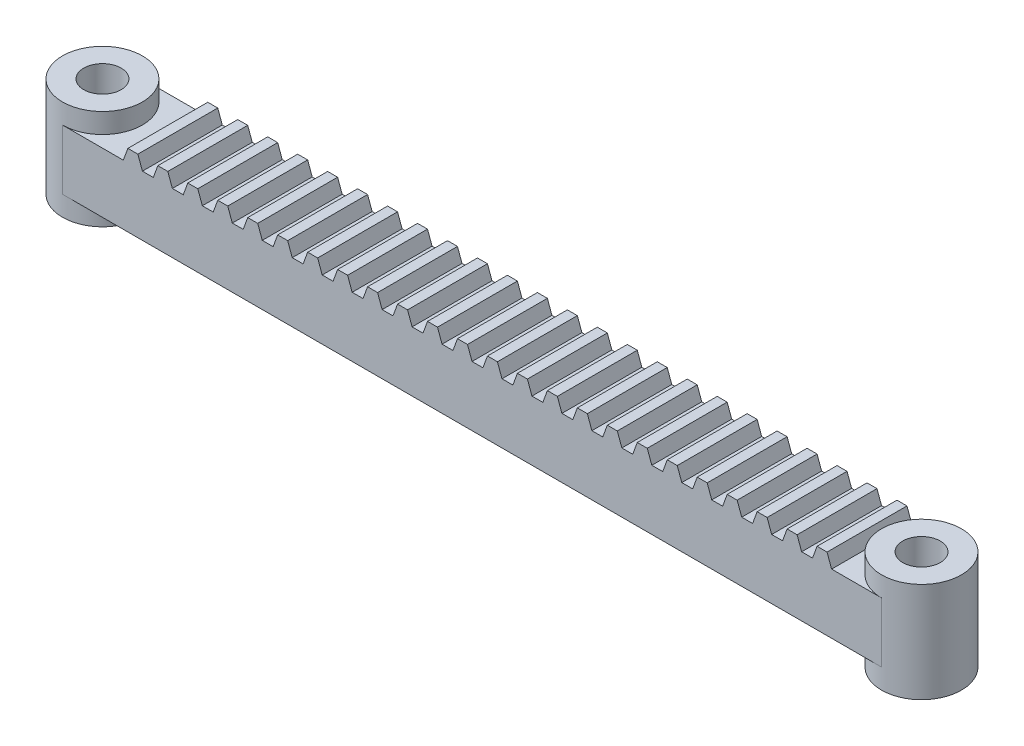
SolidWorks part; units mm, degrees
ref_plane "Płaszczyzna przednia" through (0, 0, 0) normal (0, 0, 1) x (1, 0, 0)
ref_plane "Płaszczyzna górna" through (0, 0, 0) normal (0, 1, 0) x (1, 0, 0)
ref_plane "Płaszczyzna prawa" through (0, 0, 0) normal (1, 0, 0) x (0, 0, -1)
sketch "Szkic1" plane through (0, 0, 0) normal (0, 1, 0) x (1, 0, 0)
  line L1 (-82, 8) -> (82, 8)
  line L2 (-82, 8) -> (-82, -8)
  line L3 (-82, -8) -> (82, -8)
  line L4 (82, 8) -> (82, -8)
  line L5 (-82, 8) -> (82, -8) construction
  line L6 (-82, -8) -> (82, 8) construction
  point P0 (0, 0)
  dimension "D1" = 164
  dimension "D2" = 16
extrude "Dodanie-wyciągnięcie1" add sketch "Szkic1" along normal blind 12
ref_plane "Płaszczyzna1" through (0, -4, 0) normal (0, 1, 0) x (1, 0, 0)
sketch "Szkic2" plane through (0, -4, 0) normal (0, 1, 0) x (1, 0, 0)
  line L0 (82, -8) -> (82, 8) construction
  line L1 (82, 8) -> (-82, 8) construction
  line L2 (-82, 8) -> (-82, -8) construction
  circle A0 centre (82, 0) radius 8
  circle A1 centre (82, 0) radius 3.75
  circle A2 centre (-82, 0) radius 3.75
  circle A3 centre (-82, 0) radius 8
  dimension "D1" = 7.5
  dimension "D2" = 7.5
extrude "Dodanie-wyciągnięcie3" add sketch "Szkic2" along normal blind 20
sketch "Szkic3" plane through (0, 12, 0) normal (0, 1, 0) x (1, 0, 0)
  line L1 (82, -3.75) -> (82, 3.75)
  line L2 (82, -3.75) -> (82, 3.75)
  line L3 (-82, 3.75) -> (-82, -3.75)
  line L4 (-82, 3.75) -> (-82, -3.75)
  arc A1 (82, 3.75) -> (82, -3.75) centre (82, 0) ccw
  arc A2 (82, 3.75) -> (82, -3.75) centre (82, 0) ccw
  arc A3 (-82, -3.75) -> (-82, 3.75) centre (-82, 0) ccw
  arc A4 (-82, -3.75) -> (-82, 3.75) centre (-82, 0) ccw
  dimension "D1" = 0
  dimension "D2" = 0
extrude "Wytnij-wyciągnięcie1" cut sketch "Szkic3" against normal blind 20
sketch "Szkic4" plane through (0, 0, 8) normal (0, 0, 1) x (1, 0, 0)
  line L0 (72, 12) -> (71.0901, 14.5)
  line L1 (-82, 12) -> (82, 12) construction
  line L2 (71.0901, 14.5) -> (69.0901, 14.5)
  line L3 (69.0901, 14.5) -> (68.1801, 12)
  line L4 (68.1801, 12) -> (72, 12)
  line L5 (90, -4) -> (90, 16) construction
  line L6 (62.1801, 12) -> (66, 12)
  line L7 (66, 12) -> (65.0901, 14.5)
  line L8 (65.0901, 14.5) -> (63.0901, 14.5)
  line L9 (63.0901, 14.5) -> (62.1801, 12)
  line L10 (56.1801, 12) -> (60, 12)
  line L11 (60, 12) -> (59.0901, 14.5)
  line L12 (59.0901, 14.5) -> (57.0901, 14.5)
  line L13 (57.0901, 14.5) -> (56.1801, 12)
  line L14 (50.1801, 12) -> (54, 12)
  line L15 (54, 12) -> (53.0901, 14.5)
  line L16 (53.0901, 14.5) -> (51.0901, 14.5)
  line L17 (51.0901, 14.5) -> (50.1801, 12)
  line L18 (44.1801, 12) -> (48, 12)
  line L19 (48, 12) -> (47.0901, 14.5)
  line L20 (47.0901, 14.5) -> (45.0901, 14.5)
  line L21 (45.0901, 14.5) -> (44.1801, 12)
  line L22 (38.1801, 12) -> (42, 12)
  line L23 (42, 12) -> (41.0901, 14.5)
  line L24 (41.0901, 14.5) -> (39.0901, 14.5)
  line L25 (39.0901, 14.5) -> (38.1801, 12)
  line L26 (32.1801, 12) -> (36, 12)
  line L27 (36, 12) -> (35.0901, 14.5)
  line L28 (35.0901, 14.5) -> (33.0901, 14.5)
  line L29 (33.0901, 14.5) -> (32.1801, 12)
  line L30 (26.1801, 12) -> (30, 12)
  line L31 (30, 12) -> (29.0901, 14.5)
  line L32 (29.0901, 14.5) -> (27.0901, 14.5)
  line L33 (27.0901, 14.5) -> (26.1801, 12)
  line L34 (20.1801, 12) -> (24, 12)
  line L35 (24, 12) -> (23.0901, 14.5)
  line L36 (23.0901, 14.5) -> (21.0901, 14.5)
  line L37 (21.0901, 14.5) -> (20.1801, 12)
  line L38 (14.1801, 12) -> (18, 12)
  line L39 (18, 12) -> (17.0901, 14.5)
  line L40 (17.0901, 14.5) -> (15.0901, 14.5)
  line L41 (15.0901, 14.5) -> (14.1801, 12)
  line L42 (8.1801, 12) -> (12, 12)
  line L43 (12, 12) -> (11.0901, 14.5)
  line L44 (11.0901, 14.5) -> (9.0901, 14.5)
  line L45 (9.0901, 14.5) -> (8.1801, 12)
  line L46 (2.1801, 12) -> (6, 12)
  line L47 (6, 12) -> (5.0901, 14.5)
  line L48 (5.0901, 14.5) -> (3.0901, 14.5)
  line L49 (3.0901, 14.5) -> (2.1801, 12)
  line L50 (-3.8199, 12) -> (0, 12)
  line L51 (0, 12) -> (-0.9099, 14.5)
  line L52 (-0.9099, 14.5) -> (-2.9099, 14.5)
  line L53 (-2.9099, 14.5) -> (-3.8199, 12)
  line L54 (-9.8199, 12) -> (-6, 12)
  line L55 (-6, 12) -> (-6.9099, 14.5)
  line L56 (-6.9099, 14.5) -> (-8.9099, 14.5)
  line L57 (-8.9099, 14.5) -> (-9.8199, 12)
  line L58 (-15.8199, 12) -> (-12, 12)
  line L59 (-12, 12) -> (-12.9099, 14.5)
  line L60 (-12.9099, 14.5) -> (-14.9099, 14.5)
  line L61 (-14.9099, 14.5) -> (-15.8199, 12)
  line L62 (-21.8199, 12) -> (-18, 12)
  line L63 (-18, 12) -> (-18.9099, 14.5)
  line L64 (-18.9099, 14.5) -> (-20.9099, 14.5)
  line L65 (-20.9099, 14.5) -> (-21.8199, 12)
  line L66 (-27.8199, 12) -> (-24, 12)
  line L67 (-24, 12) -> (-24.9099, 14.5)
  line L68 (-24.9099, 14.5) -> (-26.9099, 14.5)
  line L69 (-26.9099, 14.5) -> (-27.8199, 12)
  line L70 (-33.8199, 12) -> (-30, 12)
  line L71 (-30, 12) -> (-30.9099, 14.5)
  line L72 (-30.9099, 14.5) -> (-32.9099, 14.5)
  line L73 (-32.9099, 14.5) -> (-33.8199, 12)
  line L74 (-39.8199, 12) -> (-36, 12)
  line L75 (-36, 12) -> (-36.9099, 14.5)
  line L76 (-36.9099, 14.5) -> (-38.9099, 14.5)
  line L77 (-38.9099, 14.5) -> (-39.8199, 12)
  line L78 (-45.8199, 12) -> (-42, 12)
  line L79 (-42, 12) -> (-42.9099, 14.5)
  line L80 (-42.9099, 14.5) -> (-44.9099, 14.5)
  line L81 (-44.9099, 14.5) -> (-45.8199, 12)
  line L82 (-51.8199, 12) -> (-48, 12)
  line L83 (-48, 12) -> (-48.9099, 14.5)
  line L84 (-48.9099, 14.5) -> (-50.9099, 14.5)
  line L85 (-50.9099, 14.5) -> (-51.8199, 12)
  line L86 (-57.8199, 12) -> (-54, 12)
  line L87 (-54, 12) -> (-54.9099, 14.5)
  line L88 (-54.9099, 14.5) -> (-56.9099, 14.5)
  line L89 (-56.9099, 14.5) -> (-57.8199, 12)
  line L90 (-63.8199, 12) -> (-60, 12)
  line L91 (-60, 12) -> (-60.9099, 14.5)
  line L92 (-60.9099, 14.5) -> (-62.9099, 14.5)
  line L93 (-62.9099, 14.5) -> (-63.8199, 12)
  line L94 (-69.8199, 12) -> (-66, 12)
  line L95 (-66, 12) -> (-66.9099, 14.5)
  line L96 (-66.9099, 14.5) -> (-68.9099, 14.5)
  line L97 (-68.9099, 14.5) -> (-69.8199, 12)
  point P9 (0, 0)
  point P101 (0, 0)
  dimension "D1" = 40
  dimension "D2" = 18
  dimension "D3" = 2.5
  dimension "D4" = 2
  dimension "D5" = 24
  dimension "D6" = 6
extrude "Dodanie-wyciągnięcie4" add sketch "Szkic4" against normal up to surface (16 mm away) up to face at (0, 6, -8)
